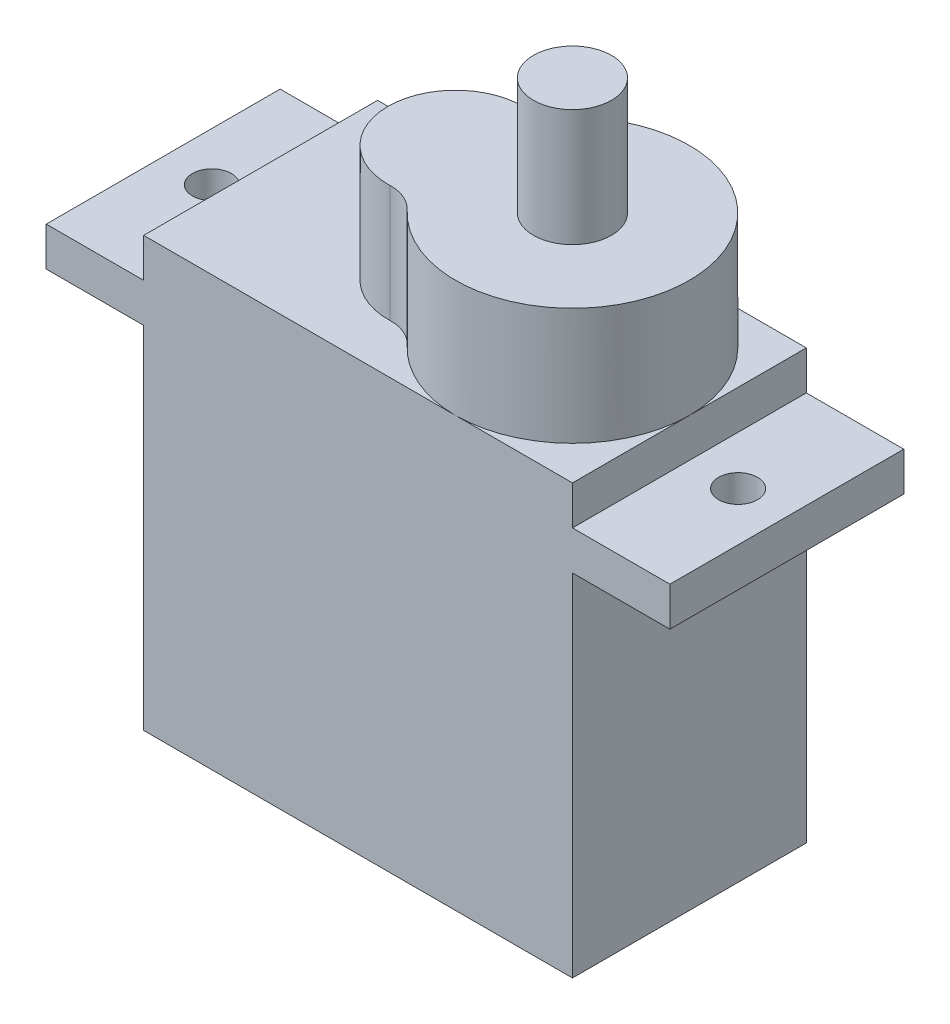
SolidWorks part; units mm, degrees
ref_plane "前视基准面" through (0, 0, 0) normal (0, 0, 1) x (1, 0, 0)
ref_plane "上视基准面" through (0, 0, 0) normal (0, 1, 0) x (1, 0, 0)
ref_plane "右视基准面" through (0, 0, 0) normal (1, 0, 0) x (0, 0, -1)
sketch "草图1" plane through (0, 0, 0) normal (0, 1, 0) x (1, 0, 0)
  line L1 (-11, 6) -> (11, 6)
  line L2 (-11, 6) -> (-11, -6)
  line L3 (-11, -6) -> (11, -6)
  line L4 (11, 6) -> (11, -6)
  line L5 (-11, 6) -> (11, -6) construction
  line L6 (-11, -6) -> (11, 6) construction
  point P0 (0, 0)
  dimension "D1" = 22
  dimension "D2" = 12
extrude "凸台-拉伸1" add sketch "草图1" along normal blind 22
ref_plane "基准面1" through (0, 20, 0) normal (0, 1, 0) x (1, 0, 0)
sketch "草图2" plane through (0, 20, 0) normal (0, 1, 0) x (1, 0, 0)
  line L0 (0, 4.5385) -> (0, -2.2982) construction
  line L1 (-11, 6) -> (-16, 6)
  line L2 (-11, 6) -> (-11, -6)
  line L3 (-11, -6) -> (-16, -6)
  line L4 (-16, 6) -> (-16, -6)
  line L5 (16, 6) -> (16, -6)
  line L6 (11, -6) -> (16, -6)
  line L7 (11, 6) -> (11, -6)
  line L8 (11, 6) -> (16, 6)
  point P0 (-11, 6)
  point P1 (-11, -6)
  dimension "D1" = 5
extrude "凸台-拉伸2" add sketch "草图2" against normal blind 2
sketch "草图3" plane through (0, 20, 0) normal (0, 1, 0) x (1, 0, 0)
  line L0 (-11, -6) -> (-11, 6) construction
  line L1 (0, 6.2923) -> (0, -1.467) construction
  circle A0 centre (-13.5, 0) radius 1
  circle A1 centre (13.5, 0) radius 1
  point P0 (-13.5, 0)
  dimension "D1" = 2.5
extrude "切除-拉伸1" cut sketch "草图3" against normal blind 2
sketch "草图4" plane through (0, 22, 0) normal (0, 1, 0) x (1, 0, 0)
  line L0 (11, -6) -> (11, 6) construction
  arc A0 (0.6167, -4.0971) -> (0.6167, 4.0971) centre (5, 0) ccw
  arc A1 (-0.9014, 3.4636) -> (-0.9014, -3.4636) centre (-1, 0) ccw
  arc A2 (0.6167, -4.0971) -> (-0.9014, -3.4636) centre (-0.8445, -5.4628) ccw
  arc A3 (-0.9014, 3.4636) -> (0.6167, 4.0971) centre (-0.8445, 5.4628) ccw
  dimension "D1" = 6
  dimension "D3" = 2
  dimension "D2" = 12
extrude "凸台-拉伸3" add sketch "草图4" along normal blind 6
sketch "草图5" plane through (0, 28, 0) normal (0, 1, 0) x (1, 0, 0)
  circle A0 centre (5, 0) radius 2
  arc A4 (0.6167, -4.0971) -> (-0.9014, -3.4636) centre (-0.8445, -5.4628) ccw
  arc A5 (0.6167, -4.0971) -> (0.6167, 4.0971) centre (5, 0) ccw
  arc A6 (-0.9014, 3.4636) -> (0.6167, 4.0971) centre (-0.8445, 5.4628) ccw
  arc A7 (-0.9014, 3.4636) -> (-0.9014, -3.4636) centre (-1, 0) ccw
  arc A8 (0.6167, -4.0971) -> (-0.9014, -3.4636) centre (-0.8445, -5.4628) ccw
  arc A9 (0.6167, -4.0971) -> (0.6167, 4.0971) centre (5, 0) ccw
  arc A10 (-0.9014, 3.4636) -> (0.6167, 4.0971) centre (-0.8445, 5.4628) ccw
  arc A11 (-0.9014, 3.4636) -> (-0.9014, -3.4636) centre (-1, 0) ccw
  dimension "D1" = 0
extrude "凸台-拉伸4" add sketch "草图5" along normal blind 6 contours A0 region at (5, 28, 0)
sketch "草图6" plane through (0, 22, 0) normal (0, 1, 0) x (1, 0, 0)
  line L0 (-11, 0) -> (11, 0)
  line L1 (-11, 6) -> (-11, -6) construction
  point P5 (11, 0)
